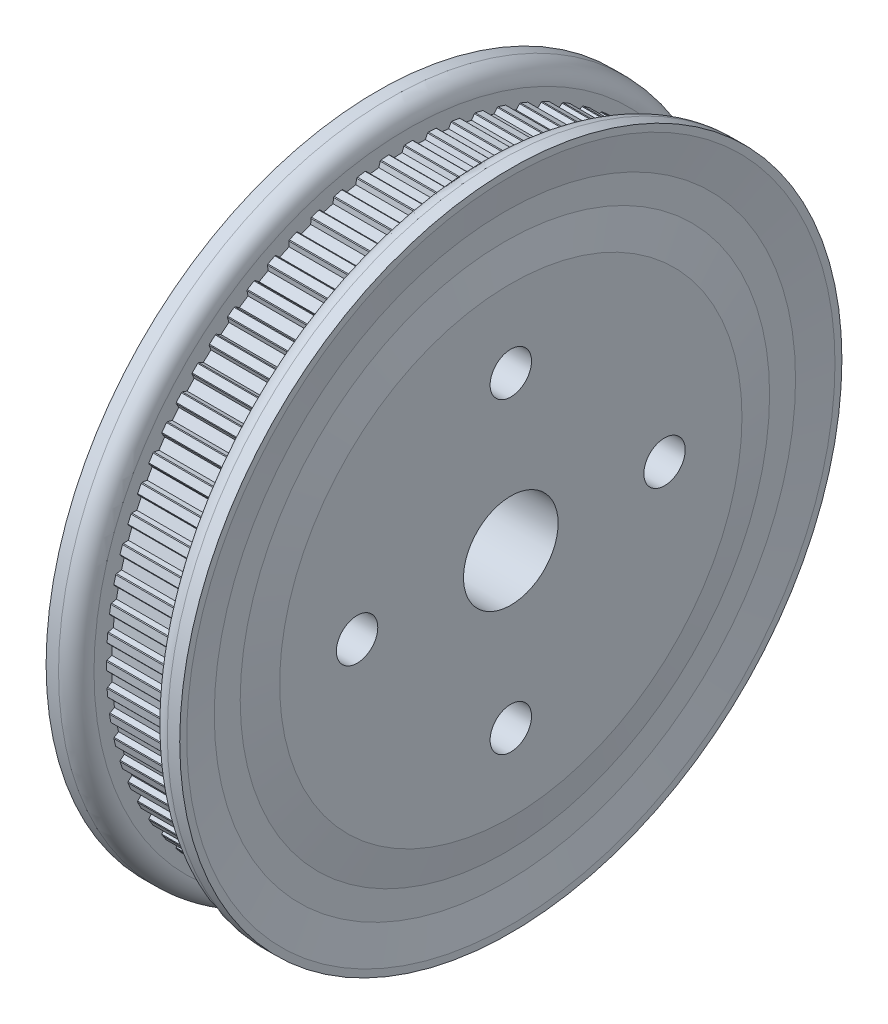
SolidWorks part; units mm, degrees
other "Câmera1"
ref_plane "Plano frontal" through (0, 0, 0) normal (0, 0, 1) x (1, 0, 0)
ref_plane "Plano superior" through (0, 0, 0) normal (0, 1, 0) x (1, 0, 0)
ref_plane "Plano direito" through (0, 0, 0) normal (1, 0, 0) x (0, 0, -1)
sketch "Esboço2" plane through (0, 0, 0) normal (1, 0, 0) x (0, 0, -1)
  line L0 (-0.3275, 25.545) -> (0.3325, 25.545)
  line L1 (-0.3949, 25.4981) -> (-0.5455, 25.0931)
  line L2 (0.3999, 25.4981) -> (0.5509, 25.0915)
  line L3 (1.6069, 25.4505) -> (1.425, 25.0585)
  line L4 (-0.3275, 25.545) -> (-0.3949, 25.4981)
  line L5 (1.425, 25.0585) -> (0.5509, 25.0915)
  line L6 (0.3325, 25.545) -> (0.3999, 25.4981)
  line L7 (1.6777, 25.4919) -> (1.6069, 25.4505)
  line L8 (1.6777, 25.4919) -> (2.3357, 25.4402)
  line L9 (2.3357, 25.4402) -> (2.3992, 25.3882)
  line L10 (2.3992, 25.3882) -> (2.5178, 24.9709)
  line L11 (3.3867, 24.8695) -> (2.5178, 24.9709)
  line L12 (3.5987, 25.246) -> (3.3867, 24.8695)
  line L13 (3.6727, 25.2817) -> (3.5987, 25.246)
  line L14 (3.6727, 25.2817) -> (4.3245, 25.1785)
  line L15 (4.3245, 25.1785) -> (4.3838, 25.1216)
  line L16 (4.3838, 25.1216) -> (4.4693, 24.6964)
  line L17 (5.3275, 24.5271) -> (4.4693, 24.6964)
  line L18 (5.5684, 24.8858) -> (5.3275, 24.5271)
  line L19 (5.6449, 24.9156) -> (5.5684, 24.8858)
  line L20 (5.6449, 24.9156) -> (6.2867, 24.7616)
  line L21 (6.2867, 24.7616) -> (6.3413, 24.7003)
  line L22 (6.3413, 24.7003) -> (6.3931, 24.2696)
  line L23 (7.2354, 24.0335) -> (6.3931, 24.2696)
  line L24 (7.5038, 24.3722) -> (7.2354, 24.0335)
  line L25 (7.5824, 24.3959) -> (7.5038, 24.3722)
  line L26 (7.5824, 24.3959) -> (8.2101, 24.192)
  line L27 (8.2101, 24.192) -> (8.2597, 24.1266)
  line L28 (8.2597, 24.1266) -> (8.2776, 23.6932)
  line L29 (9.0988, 23.3917) -> (8.2776, 23.6932)
  line L30 (9.3929, 23.7083) -> (9.0988, 23.3917)
  line L31 (9.4731, 23.7258) -> (9.3929, 23.7083)
  line L32 (9.4731, 23.7258) -> (10.0828, 23.4733)
  line L33 (10.0828, 23.4733) -> (10.1272, 23.4042)
  line L34 (10.1272, 23.4042) -> (10.111, 22.9707)
  line L35 (10.906, 22.6057) -> (10.111, 22.9707)
  line L36 (11.224, 22.8983) -> (10.906, 22.6057)
  line L37 (11.3054, 22.9094) -> (11.224, 22.8983)
  line L38 (11.3054, 22.9094) -> (11.8934, 22.6098)
  line L39 (11.8934, 22.6098) -> (11.9322, 22.5374)
  line L40 (11.9322, 22.5374) -> (11.8821, 22.1066)
  line L41 (12.646, 21.6804) -> (11.8821, 22.1066)
  line L42 (12.986, 21.9471) -> (12.646, 21.6804)
  line L43 (13.068, 21.9518) -> (12.986, 21.9471)
  line L44 (13.068, 21.9518) -> (13.6307, 21.607)
  line L45 (13.6307, 21.607) -> (13.6637, 21.5318)
  line L46 (13.6637, 21.5318) -> (13.58, 21.1062)
  line L47 (14.3081, 20.6213) -> (13.58, 21.1062)
  line L48 (14.6679, 20.8605) -> (14.3081, 20.6213)
  line L49 (14.75, 20.8588) -> (14.6679, 20.8605)
  line L50 (14.75, 20.8588) -> (15.284, 20.4709)
  line L51 (15.284, 20.4709) -> (15.311, 20.3934)
  line L52 (15.311, 20.3934) -> (15.1941, 19.9756)
  line L53 (15.8819, 19.4352) -> (15.1941, 19.9756)
  line L54 (16.2594, 19.6454) -> (15.8819, 19.4352)
  line L55 (16.3411, 19.6373) -> (16.2594, 19.6454)
  line L56 (16.3411, 19.6373) -> (16.843, 19.2086)
  line L57 (16.843, 19.2086) -> (16.8638, 19.1292)
  line L58 (16.8638, 19.1292) -> (16.7145, 18.722)
  line L59 (17.3578, 18.1292) -> (16.7145, 18.722)
  line L60 (17.7507, 18.3092) -> (17.3578, 18.1292)
  line L61 (17.8315, 18.2946) -> (17.7507, 18.3092)
  line L62 (17.8315, 18.2946) -> (18.2982, 17.8279)
  line L63 (18.2982, 17.8279) -> (18.3127, 17.7471)
  line L64 (18.3127, 17.7471) -> (18.1319, 17.3528)
  line L65 (18.7267, 16.7114) -> (18.1319, 17.3528)
  line L66 (19.1325, 16.86) -> (18.7267, 16.7114)
  line L67 (19.2119, 16.8392) -> (19.1325, 16.86)
  line L68 (19.2119, 16.8392) -> (19.6405, 16.3373)
  line L69 (19.6405, 16.3373) -> (19.6487, 16.2556)
  line L70 (19.6487, 16.2556) -> (19.4375, 15.8767)
  line L71 (19.9801, 15.1906) -> (19.4375, 15.8767)
  line L72 (20.3963, 15.3069) -> (19.9801, 15.1906)
  line L73 (20.4738, 15.2799) -> (20.3963, 15.3069)
  line L74 (20.4738, 15.2799) -> (20.8618, 14.746)
  line L75 (20.8618, 14.746) -> (20.8635, 14.6639)
  line L76 (20.8635, 14.6639) -> (20.6232, 14.3027)
  line L77 (21.1104, 13.5762) -> (20.6232, 14.3027)
  line L78 (21.5344, 13.6595) -> (21.1104, 13.5762)
  line L79 (21.6096, 13.6265) -> (21.5344, 13.6595)
  line L80 (21.6096, 13.6265) -> (21.9544, 13.0637)
  line L81 (21.9544, 13.0637) -> (21.9497, 12.9818)
  line L82 (21.9497, 12.9818) -> (21.6818, 12.6406)
  line L83 (22.1105, 11.878) -> (21.6818, 12.6406)
  line L84 (22.5397, 11.9278) -> (22.1105, 11.878)
  line L85 (22.6121, 11.889) -> (22.5397, 11.9278)
  line L86 (22.6121, 11.889) -> (22.9117, 11.3009)
  line L87 (22.9117, 11.3009) -> (22.9006, 11.2196)
  line L88 (22.9006, 11.2196) -> (22.6068, 10.9005)
  line L89 (22.9742, 10.1066) -> (22.6068, 10.9005)
  line L90 (23.4061, 10.1226) -> (22.9742, 10.1066)
  line L91 (23.4752, 10.0782) -> (23.4061, 10.1226)
  line L92 (23.4752, 10.0782) -> (23.7277, 9.4685)
  line L93 (23.7277, 9.4685) -> (23.7102, 9.3882)
  line L94 (23.7102, 9.3882) -> (23.3923, 9.0932)
  line L95 (23.6964, 8.2729) -> (23.3923, 9.0932)
  line L96 (24.1281, 8.2549) -> (23.6964, 8.2729)
  line L97 (24.1935, 8.2053) -> (24.1281, 8.2549)
  line L98 (24.1935, 8.2053) -> (24.3975, 7.5776)
  line L99 (24.3975, 7.5776) -> (24.3737, 7.499)
  line L100 (24.3737, 7.499) -> (24.0336, 7.2298)
  line L101 (24.2724, 6.3882) -> (24.0336, 7.2298)
  line L102 (24.7014, 6.3364) -> (24.2724, 6.3882)
  line L103 (24.7627, 6.2818) -> (24.7014, 6.3364)
  line L104 (24.7627, 6.2818) -> (24.9168, 5.64)
  line L105 (24.9168, 5.64) -> (24.887, 5.5636)
  line L106 (24.887, 5.5636) -> (24.5268, 5.3218)
  line L107 (24.6988, 4.4642) -> (24.5268, 5.3218)
  line L108 (25.1224, 4.3788) -> (24.6988, 4.4642)
  line L109 (25.1793, 4.3196) -> (25.1224, 4.3788)
  line L110 (25.1793, 4.3196) -> (25.2825, 3.6677)
  line L111 (25.2825, 3.6677) -> (25.2468, 3.5938)
  line L112 (25.2468, 3.5938) -> (24.8687, 3.3811)
  line L113 (24.9729, 2.5126) -> (24.8687, 3.3811)
  line L114 (25.3885, 2.3943) -> (24.9729, 2.5126)
  line L115 (25.4406, 2.3307) -> (25.3885, 2.3943)
  line L116 (25.4406, 2.3307) -> (25.4923, 1.6728)
  line L117 (25.4923, 1.6728) -> (25.4509, 1.6019)
  line L118 (25.4509, 1.6019) -> (25.0574, 1.4195)
  line L119 (25.0931, 0.5455) -> (25.0574, 1.4195)
  line L120 (25.4981, 0.3949) -> (25.0931, 0.5455)
  line L121 (25.545, 0.3275) -> (25.4981, 0.3949)
  line L122 (25.545, 0.3275) -> (25.545, -0.3325)
  line L123 (25.545, -0.3325) -> (25.4981, -0.3999)
  line L124 (25.4981, -0.3999) -> (25.0915, -0.5509)
  line L125 (25.0585, -1.425) -> (25.0915, -0.5509)
  line L126 (25.4505, -1.6069) -> (25.0585, -1.425)
  line L127 (25.4919, -1.6777) -> (25.4505, -1.6069)
  line L128 (25.4919, -1.6777) -> (25.4402, -2.3357)
  line L129 (25.4402, -2.3357) -> (25.3882, -2.3992)
  line L130 (25.3882, -2.3992) -> (24.9709, -2.5178)
  line L131 (24.8695, -3.3867) -> (24.9709, -2.5178)
  line L132 (25.246, -3.5987) -> (24.8695, -3.3867)
  line L133 (25.2817, -3.6727) -> (25.246, -3.5987)
  line L134 (25.2817, -3.6727) -> (25.1785, -4.3245)
  line L135 (25.1785, -4.3245) -> (25.1216, -4.3838)
  line L136 (25.1216, -4.3838) -> (24.6964, -4.4693)
  line L137 (24.5271, -5.3275) -> (24.6964, -4.4693)
  line L138 (24.8858, -5.5684) -> (24.5271, -5.3275)
  line L139 (24.9156, -5.6449) -> (24.8858, -5.5684)
  line L140 (24.9156, -5.6449) -> (24.7616, -6.2867)
  line L141 (24.7616, -6.2867) -> (24.7003, -6.3413)
  line L142 (24.7003, -6.3413) -> (24.2696, -6.3931)
  line L143 (24.0335, -7.2354) -> (24.2696, -6.3931)
  line L144 (24.3722, -7.5038) -> (24.0335, -7.2354)
  line L145 (24.3959, -7.5824) -> (24.3722, -7.5038)
  line L146 (24.3959, -7.5824) -> (24.192, -8.2101)
  line L147 (24.192, -8.2101) -> (24.1266, -8.2597)
  line L148 (24.1266, -8.2597) -> (23.6932, -8.2776)
  line L149 (23.3917, -9.0988) -> (23.6932, -8.2776)
  line L150 (23.7083, -9.3929) -> (23.3917, -9.0988)
  line L151 (23.7258, -9.4731) -> (23.7083, -9.3929)
  line L152 (23.7258, -9.4731) -> (23.4733, -10.0828)
  line L153 (23.4733, -10.0828) -> (23.4042, -10.1272)
  line L154 (23.4042, -10.1272) -> (22.9707, -10.111)
  line L155 (22.6057, -10.906) -> (22.9707, -10.111)
  line L156 (22.8983, -11.224) -> (22.6057, -10.906)
  line L157 (22.9094, -11.3054) -> (22.8983, -11.224)
  line L158 (22.9094, -11.3054) -> (22.6098, -11.8934)
  line L159 (22.6098, -11.8934) -> (22.5374, -11.9322)
  line L160 (22.5374, -11.9322) -> (22.1066, -11.8821)
  line L161 (21.6804, -12.646) -> (22.1066, -11.8821)
  line L162 (21.9471, -12.986) -> (21.6804, -12.646)
  line L163 (21.9518, -13.068) -> (21.9471, -12.986)
  line L164 (21.9518, -13.068) -> (21.607, -13.6307)
  line L165 (21.607, -13.6307) -> (21.5318, -13.6637)
  line L166 (21.5318, -13.6637) -> (21.1062, -13.58)
  line L167 (20.6213, -14.3081) -> (21.1062, -13.58)
  line L168 (20.8605, -14.6679) -> (20.6213, -14.3081)
  line L169 (20.8588, -14.75) -> (20.8605, -14.6679)
  line L170 (20.8588, -14.75) -> (20.4709, -15.284)
  line L171 (20.4709, -15.284) -> (20.3934, -15.311)
  line L172 (20.3934, -15.311) -> (19.9756, -15.1941)
  line L173 (19.4352, -15.8819) -> (19.9756, -15.1941)
  line L174 (19.6454, -16.2594) -> (19.4352, -15.8819)
  line L175 (19.6373, -16.3411) -> (19.6454, -16.2594)
  line L176 (19.6373, -16.3411) -> (19.2086, -16.843)
  line L177 (19.2086, -16.843) -> (19.1292, -16.8638)
  line L178 (19.1292, -16.8638) -> (18.722, -16.7145)
  line L179 (18.1292, -17.3578) -> (18.722, -16.7145)
  line L180 (18.3092, -17.7507) -> (18.1292, -17.3578)
  line L181 (18.2946, -17.8315) -> (18.3092, -17.7507)
  line L182 (18.2946, -17.8315) -> (17.8279, -18.2982)
  line L183 (17.8279, -18.2982) -> (17.7471, -18.3127)
  line L184 (17.7471, -18.3127) -> (17.3528, -18.1319)
  line L185 (16.7114, -18.7267) -> (17.3528, -18.1319)
  line L186 (16.86, -19.1325) -> (16.7114, -18.7267)
  line L187 (16.8392, -19.2119) -> (16.86, -19.1325)
  line L188 (16.8392, -19.2119) -> (16.3373, -19.6405)
  line L189 (16.3373, -19.6405) -> (16.2556, -19.6487)
  line L190 (16.2556, -19.6487) -> (15.8767, -19.4375)
  line L191 (15.1906, -19.9801) -> (15.8767, -19.4375)
  line L192 (15.3069, -20.3963) -> (15.1906, -19.9801)
  line L193 (15.2799, -20.4738) -> (15.3069, -20.3963)
  line L194 (15.2799, -20.4738) -> (14.746, -20.8618)
  line L195 (14.746, -20.8618) -> (14.6639, -20.8635)
  line L196 (14.6639, -20.8635) -> (14.3027, -20.6232)
  line L197 (13.5762, -21.1104) -> (14.3027, -20.6232)
  line L198 (13.6595, -21.5344) -> (13.5762, -21.1104)
  line L199 (13.6265, -21.6096) -> (13.6595, -21.5344)
  line L200 (13.6265, -21.6096) -> (13.0637, -21.9544)
  line L201 (13.0637, -21.9544) -> (12.9818, -21.9497)
  line L202 (12.9818, -21.9497) -> (12.6406, -21.6818)
  line L203 (11.878, -22.1105) -> (12.6406, -21.6818)
  line L204 (11.9278, -22.5397) -> (11.878, -22.1105)
  line L205 (11.889, -22.6121) -> (11.9278, -22.5397)
  line L206 (11.889, -22.6121) -> (11.3009, -22.9117)
  line L207 (11.3009, -22.9117) -> (11.2196, -22.9006)
  line L208 (11.2196, -22.9006) -> (10.9005, -22.6068)
  line L209 (10.1066, -22.9742) -> (10.9005, -22.6068)
  line L210 (10.1226, -23.4061) -> (10.1066, -22.9742)
  line L211 (10.0782, -23.4752) -> (10.1226, -23.4061)
  line L212 (10.0782, -23.4752) -> (9.4685, -23.7277)
  line L213 (9.4685, -23.7277) -> (9.3882, -23.7102)
  line L214 (9.3882, -23.7102) -> (9.0932, -23.3923)
  line L215 (8.2729, -23.6964) -> (9.0932, -23.3923)
  line L216 (8.2549, -24.1281) -> (8.2729, -23.6964)
  line L217 (8.2053, -24.1935) -> (8.2549, -24.1281)
  line L218 (8.2053, -24.1935) -> (7.5776, -24.3975)
  line L219 (7.5776, -24.3975) -> (7.499, -24.3737)
  line L220 (7.499, -24.3737) -> (7.2298, -24.0336)
  line L221 (6.3882, -24.2724) -> (7.2298, -24.0336)
  line L222 (6.3364, -24.7014) -> (6.3882, -24.2724)
  line L223 (6.2818, -24.7627) -> (6.3364, -24.7014)
  line L224 (6.2818, -24.7627) -> (5.64, -24.9168)
  line L225 (5.64, -24.9168) -> (5.5636, -24.887)
  line L226 (5.5636, -24.887) -> (5.3218, -24.5268)
  line L227 (4.4642, -24.6988) -> (5.3218, -24.5268)
  line L228 (4.3788, -25.1224) -> (4.4642, -24.6988)
  line L229 (4.3196, -25.1793) -> (4.3788, -25.1224)
  line L230 (4.3196, -25.1793) -> (3.6677, -25.2825)
  line L231 (3.6677, -25.2825) -> (3.5938, -25.2468)
  line L232 (3.5938, -25.2468) -> (3.3811, -24.8687)
  line L233 (2.5126, -24.9729) -> (3.3811, -24.8687)
  line L234 (2.3943, -25.3885) -> (2.5126, -24.9729)
  line L235 (2.3307, -25.4406) -> (2.3943, -25.3885)
  line L236 (2.3307, -25.4406) -> (1.6728, -25.4923)
  line L237 (1.6728, -25.4923) -> (1.6019, -25.4509)
  line L238 (1.6019, -25.4509) -> (1.4195, -25.0574)
  line L239 (0.5455, -25.0931) -> (1.4195, -25.0574)
  line L240 (0.3949, -25.4981) -> (0.5455, -25.0931)
  line L241 (0.3275, -25.545) -> (0.3949, -25.4981)
  line L242 (0.3275, -25.545) -> (-0.3325, -25.545)
  line L243 (-0.3325, -25.545) -> (-0.3999, -25.4981)
  line L244 (-0.3999, -25.4981) -> (-0.5509, -25.0915)
  line L245 (-1.425, -25.0585) -> (-0.5509, -25.0915)
  line L246 (-1.6069, -25.4505) -> (-1.425, -25.0585)
  line L247 (-1.6777, -25.4919) -> (-1.6069, -25.4505)
  line L248 (-1.6777, -25.4919) -> (-2.3357, -25.4402)
  line L249 (-2.3357, -25.4402) -> (-2.3992, -25.3882)
  line L250 (-2.3992, -25.3882) -> (-2.5178, -24.9709)
  line L251 (-3.3867, -24.8695) -> (-2.5178, -24.9709)
  line L252 (-3.5987, -25.246) -> (-3.3867, -24.8695)
  line L253 (-3.6727, -25.2817) -> (-3.5987, -25.246)
  line L254 (-3.6727, -25.2817) -> (-4.3245, -25.1785)
  line L255 (-4.3245, -25.1785) -> (-4.3838, -25.1216)
  line L256 (-4.3838, -25.1216) -> (-4.4693, -24.6964)
  line L257 (-5.3275, -24.5271) -> (-4.4693, -24.6964)
  line L258 (-5.5684, -24.8858) -> (-5.3275, -24.5271)
  line L259 (-5.6449, -24.9156) -> (-5.5684, -24.8858)
  line L260 (-5.6449, -24.9156) -> (-6.2867, -24.7616)
  line L261 (-6.2867, -24.7616) -> (-6.3413, -24.7003)
  line L262 (-6.3413, -24.7003) -> (-6.3931, -24.2696)
  line L263 (-7.2354, -24.0335) -> (-6.3931, -24.2696)
  line L264 (-7.5038, -24.3722) -> (-7.2354, -24.0335)
  line L265 (-7.5824, -24.3959) -> (-7.5038, -24.3722)
  line L266 (-7.5824, -24.3959) -> (-8.2101, -24.192)
  line L267 (-8.2101, -24.192) -> (-8.2597, -24.1266)
  line L268 (-8.2597, -24.1266) -> (-8.2776, -23.6932)
  line L269 (-9.0988, -23.3917) -> (-8.2776, -23.6932)
  line L270 (-9.3929, -23.7083) -> (-9.0988, -23.3917)
  line L271 (-9.4731, -23.7258) -> (-9.3929, -23.7083)
  line L272 (-9.4731, -23.7258) -> (-10.0828, -23.4733)
  line L273 (-10.0828, -23.4733) -> (-10.1272, -23.4042)
  line L274 (-10.1272, -23.4042) -> (-10.111, -22.9707)
  line L275 (-10.906, -22.6057) -> (-10.111, -22.9707)
  line L276 (-11.224, -22.8983) -> (-10.906, -22.6057)
  line L277 (-11.3054, -22.9094) -> (-11.224, -22.8983)
  line L278 (-11.3054, -22.9094) -> (-11.8934, -22.6098)
  line L279 (-11.8934, -22.6098) -> (-11.9322, -22.5374)
  line L280 (-11.9322, -22.5374) -> (-11.8821, -22.1066)
  line L281 (-12.646, -21.6804) -> (-11.8821, -22.1066)
  line L282 (-12.986, -21.9471) -> (-12.646, -21.6804)
  line L283 (-13.068, -21.9518) -> (-12.986, -21.9471)
  line L284 (-13.068, -21.9518) -> (-13.6307, -21.607)
  line L285 (-13.6307, -21.607) -> (-13.6637, -21.5318)
  line L286 (-13.6637, -21.5318) -> (-13.58, -21.1062)
  line L287 (-14.3081, -20.6213) -> (-13.58, -21.1062)
  line L288 (-14.6679, -20.8605) -> (-14.3081, -20.6213)
  line L289 (-14.75, -20.8588) -> (-14.6679, -20.8605)
  line L290 (-14.75, -20.8588) -> (-15.284, -20.4709)
  line L291 (-15.284, -20.4709) -> (-15.311, -20.3934)
  line L292 (-15.311, -20.3934) -> (-15.1941, -19.9756)
  line L293 (-15.8819, -19.4352) -> (-15.1941, -19.9756)
  line L294 (-16.2594, -19.6454) -> (-15.8819, -19.4352)
  line L295 (-16.3411, -19.6373) -> (-16.2594, -19.6454)
  line L296 (-16.3411, -19.6373) -> (-16.843, -19.2086)
  line L297 (-16.843, -19.2086) -> (-16.8638, -19.1292)
  line L298 (-16.8638, -19.1292) -> (-16.7145, -18.722)
  line L299 (-17.3578, -18.1292) -> (-16.7145, -18.722)
  line L300 (-17.7507, -18.3092) -> (-17.3578, -18.1292)
  line L301 (-17.8315, -18.2946) -> (-17.7507, -18.3092)
  line L302 (-17.8315, -18.2946) -> (-18.2982, -17.8279)
  line L303 (-18.2982, -17.8279) -> (-18.3127, -17.7471)
  line L304 (-18.3127, -17.7471) -> (-18.1319, -17.3528)
  line L305 (-18.7267, -16.7114) -> (-18.1319, -17.3528)
  line L306 (-19.1325, -16.86) -> (-18.7267, -16.7114)
  line L307 (-19.2119, -16.8392) -> (-19.1325, -16.86)
  line L308 (-19.2119, -16.8392) -> (-19.6405, -16.3373)
  line L309 (-19.6405, -16.3373) -> (-19.6487, -16.2556)
  line L310 (-19.6487, -16.2556) -> (-19.4375, -15.8767)
  line L311 (-19.9801, -15.1906) -> (-19.4375, -15.8767)
  line L312 (-20.3963, -15.3069) -> (-19.9801, -15.1906)
  line L313 (-20.4738, -15.2799) -> (-20.3963, -15.3069)
  line L314 (-20.4738, -15.2799) -> (-20.8618, -14.746)
  line L315 (-20.8618, -14.746) -> (-20.8635, -14.6639)
  line L316 (-20.8635, -14.6639) -> (-20.6232, -14.3027)
  line L317 (-21.1104, -13.5762) -> (-20.6232, -14.3027)
  line L318 (-21.5344, -13.6595) -> (-21.1104, -13.5762)
  line L319 (-21.6096, -13.6265) -> (-21.5344, -13.6595)
  line L320 (-21.6096, -13.6265) -> (-21.9544, -13.0637)
  line L321 (-21.9544, -13.0637) -> (-21.9497, -12.9818)
  line L322 (-21.9497, -12.9818) -> (-21.6818, -12.6406)
  line L323 (-22.1105, -11.878) -> (-21.6818, -12.6406)
  line L324 (-22.5397, -11.9278) -> (-22.1105, -11.878)
  line L325 (-22.6121, -11.889) -> (-22.5397, -11.9278)
  line L326 (-22.6121, -11.889) -> (-22.9117, -11.3009)
  line L327 (-22.9117, -11.3009) -> (-22.9006, -11.2196)
  line L328 (-22.9006, -11.2196) -> (-22.6068, -10.9005)
  line L329 (-22.9742, -10.1066) -> (-22.6068, -10.9005)
  line L330 (-23.4061, -10.1226) -> (-22.9742, -10.1066)
  line L331 (-23.4752, -10.0782) -> (-23.4061, -10.1226)
  line L332 (-23.4752, -10.0782) -> (-23.7277, -9.4685)
  line L333 (-23.7277, -9.4685) -> (-23.7102, -9.3882)
  line L334 (-23.7102, -9.3882) -> (-23.3923, -9.0932)
  line L335 (-23.6964, -8.2729) -> (-23.3923, -9.0932)
  line L336 (-24.1281, -8.2549) -> (-23.6964, -8.2729)
  line L337 (-24.1935, -8.2053) -> (-24.1281, -8.2549)
  line L338 (-24.1935, -8.2053) -> (-24.3975, -7.5776)
  line L339 (-24.3975, -7.5776) -> (-24.3737, -7.499)
  line L340 (-24.3737, -7.499) -> (-24.0336, -7.2298)
  line L341 (-24.2724, -6.3882) -> (-24.0336, -7.2298)
  line L342 (-24.7014, -6.3364) -> (-24.2724, -6.3882)
  line L343 (-24.7627, -6.2818) -> (-24.7014, -6.3364)
  line L344 (-24.7627, -6.2818) -> (-24.9168, -5.64)
  line L345 (-24.9168, -5.64) -> (-24.887, -5.5636)
  line L346 (-24.887, -5.5636) -> (-24.5268, -5.3218)
  line L347 (-24.6988, -4.4642) -> (-24.5268, -5.3218)
  line L348 (-25.1224, -4.3788) -> (-24.6988, -4.4642)
  line L349 (-25.1793, -4.3196) -> (-25.1224, -4.3788)
  line L350 (-25.1793, -4.3196) -> (-25.2825, -3.6677)
  line L351 (-25.2825, -3.6677) -> (-25.2468, -3.5938)
  line L352 (-25.2468, -3.5938) -> (-24.8687, -3.3811)
  line L353 (-24.9729, -2.5126) -> (-24.8687, -3.3811)
  line L354 (-25.3885, -2.3943) -> (-24.9729, -2.5126)
  line L355 (-25.4406, -2.3307) -> (-25.3885, -2.3943)
  line L356 (-25.4406, -2.3307) -> (-25.4923, -1.6728)
  line L357 (-25.4923, -1.6728) -> (-25.4509, -1.6019)
  line L358 (-25.4509, -1.6019) -> (-25.0574, -1.4195)
  line L359 (-25.0931, -0.5455) -> (-25.0574, -1.4195)
  line L360 (-25.4981, -0.3949) -> (-25.0931, -0.5455)
  line L361 (-25.545, -0.3275) -> (-25.4981, -0.3949)
  line L362 (-25.545, -0.3275) -> (-25.545, 0.3325)
  line L363 (-25.545, 0.3325) -> (-25.4981, 0.3999)
  line L364 (-25.4981, 0.3999) -> (-25.0915, 0.5509)
  line L365 (-25.0585, 1.425) -> (-25.0915, 0.5509)
  line L366 (-25.4505, 1.6069) -> (-25.0585, 1.425)
  line L367 (-25.4919, 1.6777) -> (-25.4505, 1.6069)
  line L368 (-25.4919, 1.6777) -> (-25.4402, 2.3357)
  line L369 (-25.4402, 2.3357) -> (-25.3882, 2.3992)
  line L370 (-25.3882, 2.3992) -> (-24.9709, 2.5178)
  line L371 (-24.8695, 3.3867) -> (-24.9709, 2.5178)
  line L372 (-25.246, 3.5987) -> (-24.8695, 3.3867)
  line L373 (-25.2817, 3.6727) -> (-25.246, 3.5987)
  line L374 (-25.2817, 3.6727) -> (-25.1785, 4.3245)
  line L375 (-25.1785, 4.3245) -> (-25.1216, 4.3838)
  line L376 (-25.1216, 4.3838) -> (-24.6964, 4.4693)
  line L377 (-24.5271, 5.3275) -> (-24.6964, 4.4693)
  line L378 (-24.8858, 5.5684) -> (-24.5271, 5.3275)
  line L379 (-24.9156, 5.6449) -> (-24.8858, 5.5684)
  line L380 (-24.9156, 5.6449) -> (-24.7616, 6.2867)
  line L381 (-24.7616, 6.2867) -> (-24.7003, 6.3413)
  line L382 (-24.7003, 6.3413) -> (-24.2696, 6.3931)
  line L383 (-24.0335, 7.2354) -> (-24.2696, 6.3931)
  line L384 (-24.3722, 7.5038) -> (-24.0335, 7.2354)
  line L385 (-24.3959, 7.5824) -> (-24.3722, 7.5038)
  line L386 (-24.3959, 7.5824) -> (-24.192, 8.2101)
  line L387 (-24.192, 8.2101) -> (-24.1266, 8.2597)
  line L388 (-24.1266, 8.2597) -> (-23.6932, 8.2776)
  line L389 (-23.3917, 9.0988) -> (-23.6932, 8.2776)
  line L390 (-23.7083, 9.3929) -> (-23.3917, 9.0988)
  line L391 (-23.7258, 9.4731) -> (-23.7083, 9.3929)
  line L392 (-23.7258, 9.4731) -> (-23.4733, 10.0828)
  line L393 (-23.4733, 10.0828) -> (-23.4042, 10.1272)
  line L394 (-23.4042, 10.1272) -> (-22.9707, 10.111)
  line L395 (-22.6057, 10.906) -> (-22.9707, 10.111)
  line L396 (-22.8983, 11.224) -> (-22.6057, 10.906)
  line L397 (-22.9094, 11.3054) -> (-22.8983, 11.224)
  line L398 (-22.9094, 11.3054) -> (-22.6098, 11.8934)
  line L399 (-22.6098, 11.8934) -> (-22.5374, 11.9322)
  line L400 (-22.5374, 11.9322) -> (-22.1066, 11.8821)
  line L401 (-21.6804, 12.646) -> (-22.1066, 11.8821)
  line L402 (-21.9471, 12.986) -> (-21.6804, 12.646)
  line L403 (-21.9518, 13.068) -> (-21.9471, 12.986)
  line L404 (-21.9518, 13.068) -> (-21.607, 13.6307)
  line L405 (-21.607, 13.6307) -> (-21.5318, 13.6637)
  line L406 (-21.5318, 13.6637) -> (-21.1062, 13.58)
  line L407 (-20.6213, 14.3081) -> (-21.1062, 13.58)
  line L408 (-20.8605, 14.6679) -> (-20.6213, 14.3081)
  line L409 (-20.8588, 14.75) -> (-20.8605, 14.6679)
  line L410 (-20.8588, 14.75) -> (-20.4709, 15.284)
  line L411 (-20.4709, 15.284) -> (-20.3934, 15.311)
  line L412 (-20.3934, 15.311) -> (-19.9756, 15.1941)
  line L413 (-19.4352, 15.8819) -> (-19.9756, 15.1941)
  line L414 (-19.6454, 16.2594) -> (-19.4352, 15.8819)
  line L415 (-19.6373, 16.3411) -> (-19.6454, 16.2594)
  line L416 (-19.6373, 16.3411) -> (-19.2086, 16.843)
  line L417 (-19.2086, 16.843) -> (-19.1292, 16.8638)
  line L418 (-19.1292, 16.8638) -> (-18.722, 16.7145)
  line L419 (-18.1292, 17.3578) -> (-18.722, 16.7145)
  line L420 (-18.3092, 17.7507) -> (-18.1292, 17.3578)
  line L421 (-18.2946, 17.8315) -> (-18.3092, 17.7507)
  line L422 (-18.2946, 17.8315) -> (-17.8279, 18.2982)
  line L423 (-17.8279, 18.2982) -> (-17.7471, 18.3127)
  line L424 (-17.7471, 18.3127) -> (-17.3528, 18.1319)
  line L425 (-16.7114, 18.7267) -> (-17.3528, 18.1319)
  line L426 (-16.86, 19.1325) -> (-16.7114, 18.7267)
  line L427 (-16.8392, 19.2119) -> (-16.86, 19.1325)
  line L428 (-16.8392, 19.2119) -> (-16.3373, 19.6405)
  line L429 (-16.3373, 19.6405) -> (-16.2556, 19.6487)
  line L430 (-16.2556, 19.6487) -> (-15.8767, 19.4375)
  line L431 (-15.1906, 19.9801) -> (-15.8767, 19.4375)
  line L432 (-15.3069, 20.3963) -> (-15.1906, 19.9801)
  line L433 (-15.2799, 20.4738) -> (-15.3069, 20.3963)
  line L434 (-15.2799, 20.4738) -> (-14.746, 20.8618)
  line L435 (-14.746, 20.8618) -> (-14.6639, 20.8635)
  line L436 (-14.6639, 20.8635) -> (-14.3027, 20.6232)
  line L437 (-13.5762, 21.1104) -> (-14.3027, 20.6232)
  line L438 (-13.6595, 21.5344) -> (-13.5762, 21.1104)
  line L439 (-13.6265, 21.6096) -> (-13.6595, 21.5344)
  line L440 (-13.6265, 21.6096) -> (-13.0637, 21.9544)
  line L441 (-13.0637, 21.9544) -> (-12.9818, 21.9497)
  line L442 (-12.9818, 21.9497) -> (-12.6406, 21.6818)
  line L443 (-11.878, 22.1105) -> (-12.6406, 21.6818)
  line L444 (-11.9278, 22.5397) -> (-11.878, 22.1105)
  line L445 (-11.889, 22.6121) -> (-11.9278, 22.5397)
  line L446 (-11.889, 22.6121) -> (-11.3009, 22.9117)
  line L447 (-11.3009, 22.9117) -> (-11.2196, 22.9006)
  line L448 (-11.2196, 22.9006) -> (-10.9005, 22.6068)
  line L449 (-10.1066, 22.9742) -> (-10.9005, 22.6068)
  line L450 (-10.1226, 23.4061) -> (-10.1066, 22.9742)
  line L451 (-10.0782, 23.4752) -> (-10.1226, 23.4061)
  line L452 (-10.0782, 23.4752) -> (-9.4685, 23.7277)
  line L453 (-9.4685, 23.7277) -> (-9.3882, 23.7102)
  line L454 (-9.3882, 23.7102) -> (-9.0932, 23.3923)
  line L455 (-8.2729, 23.6964) -> (-9.0932, 23.3923)
  line L456 (-8.2549, 24.1281) -> (-8.2729, 23.6964)
  line L457 (-8.2053, 24.1935) -> (-8.2549, 24.1281)
  line L458 (-8.2053, 24.1935) -> (-7.5776, 24.3975)
  line L459 (-7.5776, 24.3975) -> (-7.499, 24.3737)
  line L460 (-7.499, 24.3737) -> (-7.2298, 24.0336)
  line L461 (-6.3882, 24.2724) -> (-7.2298, 24.0336)
  line L462 (-6.3364, 24.7014) -> (-6.3882, 24.2724)
  line L463 (-6.2818, 24.7627) -> (-6.3364, 24.7014)
  line L464 (-6.2818, 24.7627) -> (-5.64, 24.9168)
  line L465 (-5.64, 24.9168) -> (-5.5636, 24.887)
  line L466 (-5.5636, 24.887) -> (-5.3218, 24.5268)
  line L467 (-4.4642, 24.6988) -> (-5.3218, 24.5268)
  line L468 (-4.3788, 25.1224) -> (-4.4642, 24.6988)
  line L469 (-4.3196, 25.1793) -> (-4.3788, 25.1224)
  line L470 (-4.3196, 25.1793) -> (-3.6677, 25.2825)
  line L471 (-3.6677, 25.2825) -> (-3.5938, 25.2468)
  line L472 (-3.5938, 25.2468) -> (-3.3811, 24.8687)
  line L473 (-2.5126, 24.9729) -> (-3.3811, 24.8687)
  line L474 (-2.3943, 25.3885) -> (-2.5126, 24.9729)
  line L475 (-2.3307, 25.4406) -> (-2.3943, 25.3885)
  line L476 (-2.3307, 25.4406) -> (-1.6728, 25.4923)
  line L477 (-1.6728, 25.4923) -> (-1.6019, 25.4509)
  line L478 (-1.6019, 25.4509) -> (-1.4195, 25.0574)
  line L479 (-0.5455, 25.0931) -> (-1.4195, 25.0574)
  arc A0 (0.3357, 25.5428) -> (-0.3306, 25.5429) centre (0, 0) ccw
  point P1 (0.3825, 25.545)
  point P2 (-0.3775, 25.545)
  point P15 (1.425, 25.0585)
  point P569 (0, 0)
  dimension "D2" = 80
  dimension "D1" = 0.76
extrude "Ressalto-extrusão1" add sketch "Esboço2" along normal blind 6 contours L6 A0 L4 L1 L479 L478 L477 L476 L475 L474 L473 L472 L471 L470 L469 L468 L467 L466 L465 L464 L463 L462 L461 L460 L459 L458 L457 L456 L455 L454 L453 L452 L451 L450 L449 L448 L447 L446 L445 L444 L443 L442 L441 L440 L439 L438 L437 L436 L435 L434 region at (0, 0, 0)
sketch "Esboço10" plane through (6, 0, 0) normal (1, 0, 0) x (0, 0, -1)
  circle A0 centre (0, 0) radius 5
  dimension "D1" = 10
extrude "Ressalto-extrusão4" add sketch "Esboço10" along normal blind 0.1
sketch "Esboço14" plane through (0, 0, 0) normal (-1, 0, 0) x (0, 0, 1)
  circle A0 centre (0, 0) radius 5
  dimension "D1" = 10
extrude "Ressalto-extrusão9" add sketch "Esboço14" along normal blind 0.1
sketch "Esboço25" plane through (-0.1, 0, 0) normal (-1, 0, 0) x (0, 0, 1)
  circle A0 centre (0, 0) radius 28
  dimension "D1" = 56
extrude "Ressalto-extrusão12" add sketch "Esboço25" along normal blind 2.55
sketch "Esboço26" plane through (6.1, 0, 0) normal (1, 0, 0) x (0, 0, -1)
  circle A0 centre (0, 0) radius 28
  dimension "D1" = 56
extrude "Ressalto-extrusão13" add sketch "Esboço26" along normal blind 2.55
fillet "Filete14" radius 1.5 2 edges at (6.1, 0, -28) (-0.1, 0, 28)
sketch "Esboço28" plane through (-2.65, 0, 0) normal (-1, 0, 0) x (0, 0, 1)
  circle A0 centre (0, 0) radius 24.25
  dimension "D1" = 48.5
extrude "Corte-extrusão16" cut sketch "Esboço28" against normal blind 0.5
chamfer "Chanfro8" distance 3 angle 10 1 edges at (-2.65, 0, 24.25) first distance on face at (-2.65, 0, 24.25)
sketch "Esboço30" plane through (8.65, 0, 0) normal (1, 0, 0) x (0, 0, -1)
  circle A0 centre (0, 0) radius 24.415
  dimension "D1" = 48.83
extrude "Corte-extrusão17" cut sketch "Esboço30" against normal blind 0.5
chamfer "Chanfro9" distance 3 angle 10 1 edges at (8.65, 0, -24.415) first distance on face at (8.65, 0, -24.415)
sketch "Esboço31" plane through (8.15, 0, 0) normal (1, 0, 0) x (0, 0, -1)
  circle A0 centre (0, 0) radius 22.385
  dimension "D1" = 44.77
extrude "Ressalto-extrusão16" add sketch "Esboço31" along normal blind 0.5 draft 80
sketch "Esboço34" plane through (8.65, 0, 0) normal (1, 0, 0) x (0, 0, -1)
  circle A0 centre (0, 0) radius 4
  dimension "D1" = 8
extrude "Corte-extrusão18" cut sketch "Esboço34" against normal through all both and the other way through all
ref_plane "Plano1" through (-12.7, 0, 0) normal (0, -1, 0) x (0, 0, -1)
sketch "Esboço48" plane through (-2.15, 0, 0) normal (-1, 0, 0) x (0, 0, 1)
  circle A0 centre (0, 0) radius 22
  dimension "D1" = 44
extrude "Ressalto-extrusão18" add sketch "Esboço48" along normal blind 0.4
fillet "Filete16" radius 10 1 edges at (-2.55, 0, 22)
sketch "Schizzo1" plane through (8.65, 0, 0) normal (1, 0, 0) x (0, 0, -1)
  circle A0 centre (0, 0) radius 13 construction
  circle A1 centre (-13, 0) radius 1.75
  circle A2 centre (0, 13) radius 1.75
  circle A3 centre (13, 0) radius 1.75
  circle A4 centre (0, -13) radius 1.75
  dimension "D1" = 26
  dimension "D2" = 3.5
extrude "Taglio-Estrusione1" cut sketch "Schizzo1" against normal through all both and the other way through all
sketch "Schizzo2" plane through (8.65, 0, 0) normal (1, 0, 0) x (0, 0, -1)
  circle A0 centre (0, 0) radius 4
  circle A1 centre (0, 0) radius 4 construction
extrude "Taglio-Estrusione2" cut sketch "Schizzo2" against normal through all both and the other way through all
